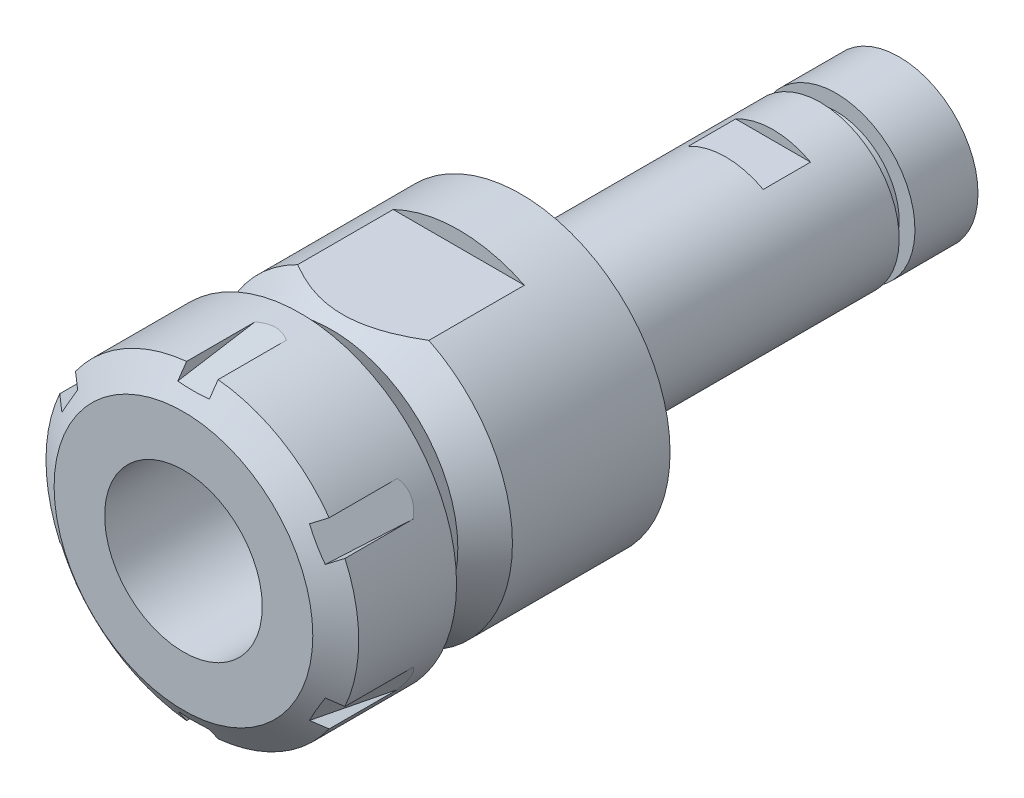
SolidWorks part; units mm, degrees
material "Chrome Stainless Steel"
ref_plane "Front Plane" through (0, 0, 0) normal (0, 0, 1) x (1, 0, 0)
ref_plane "Top Plane" through (0, 0, 0) normal (0, 1, 0) x (1, 0, 0)
ref_plane "Right Plane" through (0, 0, 0) normal (1, 0, 0) x (0, 0, -1)
sketch "Sketch1" plane through (0, 0, 0) normal (0, 0, 1) x (1, 0, 0)
  circle A0 centre (0, 0) radius 15.875
  dimension "D1" = 31.75
extrude "Boss-Extrude1" add sketch "Sketch1" along normal blind 101.6
sketch "Sketch2" plane through (0, 0, 101.6) normal (0, 0, 1) x (1, 0, 0)
  circle A0 centre (0, 0) radius 30.0482
  dimension "D1" = 60.0964
extrude "Boss-Extrude2" add sketch "Sketch2" along normal blind 31.75
sketch "Sketch5" plane through (0, 0, 0) normal (1, 0, 0) x (0, 0, -1)
  line L0 (-133.35, 30.0482) -> (-139.7, 25.4)
  line L1 (-139.7, 25.4) -> (-146.05, 30.0482)
  line L2 (-146.05, 30.0482) -> (-146.05, 0)
  line L3 (-146.05, 0) -> (-133.35, 0)
  line L4 (-133.35, 30.0482) -> (-133.35, -30.0482) construction
  line L5 (-133.35, 30.0482) -> (-133.35, 0)
  dimension "D1" = 12.7
  dimension "D2" = 6.35
  dimension "D3" = 4.6482
  dimension "D4" = 30.0482
revolve "Revolve1" add sketch "Sketch5" angle 360 about L3
sketch "Sketch6" plane through (0, 0, 146.05) normal (0, 0, 1) x (1, 0, 0)
  circle A0 centre (0, 0) radius 31.496
  dimension "D1" = 62.992
extrude "Boss-Extrude3" add sketch "Sketch6" along normal blind 23.5204
fillet "Fillet1" radius 2.54 1 edges at (15.875, 0, 0)
sketch "Sketch7" plane through (0, 0, 0) normal (0, 0, -1) x (-1, 0, 0)
  circle A0 centre (0, 0) radius 6.35
  dimension "D1" = 12.7
extrude "Cut-Extrude1" cut sketch "Sketch7" against normal blind 169.5704
sketch "Sketch8" plane through (0, 0, 169.5704) normal (0, 0, 1) x (1, 0, 0)
  circle A0 centre (0, 0) radius 15.875
  dimension "D1" = 31.75
extrude "Cut-Extrude2" cut sketch "Sketch8" against normal blind 36.2204
sketch "Sketch9" plane through (0, 0, 0) normal (1, 0, 0) x (0, 0, -1)
  line L0 (-114.1165, 30.0482) -> (-114.1165, -30.0482)
  line L1 (-101.6, 30.0482) -> (-133.35, 30.0482)
  line L2 (-101.6, 30.0482) -> (-101.6, -30.0482)
  line L3 (-101.6, -30.0482) -> (-133.35, -30.0482)
  line L4 (-133.35, 30.0482) -> (-133.35, -30.0482)
  line L5 (-133.35, 26.9875) -> (-114.1165, 26.9875)
  line L6 (-133.35, 0) -> (-114.1165, 0) construction
  line L7 (-133.35, 26.9875) -> (-137.5313, 26.9875)
  line L8 (-133.35, 30.0482) -> (-139.7, 25.4) construction
  line L9 (-137.5313, 26.9875) -> (-133.35, 30.0482)
  line L10 (-133.35, 30.0482) -> (-114.1165, 30.0482)
  line L11 (-133.35, -30.0482) -> (-114.1165, -30.0482)
  line L12 (-137.5313, -26.9875) -> (-133.35, -30.0482)
  line L13 (-133.35, -26.9875) -> (-137.5313, -26.9875)
  line L14 (-133.35, -26.9875) -> (-114.1165, -26.9875)
  dimension "D1" = 26.9875
extrude "Cut-Extrude3" cut sketch "Sketch9" against normal blind 48.26 and the other way blind 54.102 contours L4 L5 L0 L1 | L9 L7 L4 | L4 L13 L12 | L14 L4 L3 L0 region at (0, 28.5178, 123.7332) region at (0, 28.0077, 134.7438) region at (0, -28.5178, 123.7332) region at (0, -28.0077, 134.7438)
chamfer "Chamfer1" distance 3.81 angle 55 1 edges at (31.496, 0, 169.5704) first distance on face at (31.496, 0, 169.5704)
sketch "Sketch10" plane through (0, 0, 0) normal (1, 0, 0) x (0, 0, -1)
  line L0 (-151.0264, 31.496) -> (-167.6654, 28.7754)
  line L1 (-146.05, 31.496) -> (-165.7604, 31.496) construction
  line L2 (-165.7604, 31.496) -> (-169.5704, 26.0548) construction
  line L3 (-167.6654, 28.7754) -> (-167.6654, 34.7195)
  line L4 (-167.6654, 34.7195) -> (-151.0264, 31.496)
extrude "Cut-Extrude4" cut sketch "Sketch10" against normal blind 3.175 and the other way blind 3.175
pattern_circular "CirPattern1" count 6 over 360 about axis through (0, 0, 169.5704) along (0, 0, 1) of "Cut-Extrude4"
sketch "Sketch11" plane through (0, 26.9875, 0) normal (0, 1, 0) x (1, 0, 0)
  line L0 (15.875, -101.6) -> (15.875, -2.54) construction
  line L1 (15.875, -25.4) -> (-15.875, -25.4)
  line L2 (15.875, -25.4) -> (15.875, 0)
  line L3 (15.875, 0) -> (-15.875, 0)
  line L4 (-15.875, -25.4) -> (-15.875, 0)
  line L5 (13.335, 0) -> (-13.335, 0) construction
  dimension "D1" = 25.4
extrude "Cut-Extrude5" cut sketch "Sketch11" against normal blind 97.536
ref_axis "Axis1" through (0, 0, -8.4785) along (0, 0, 1)
ref_plane "Plane1" through (0, 0, 38.1) normal (0, 0, -1) x (-1, 0, 0)
sketch "Sketch12" plane through (0, 0, 38.1) normal (0, 0, -1) x (-1, 0, 0)
  circle A0 centre (0, 0) radius 19.1517
  circle A1 centre (0, 0) radius 12.7
  dimension "D1" = 25.4
extrude "Cut-Extrude6" cut sketch "Sketch12" against normal blind 3.175
ref_plane "Plane2" through (0, 0, 50.8) normal (0, 0, -1) x (-1, 0, 0)
sketch "Sketch13" plane through (0, 0, 50.8) normal (0, 0, -1) x (-1, 0, 0)
  line L0 (0, 6.35) -> (0, 13.97)
  line L1 (0, 13.97) -> (-7.5402, 13.97)
  line L2 (0, 13.97) -> (7.5402, 13.97)
  circle A0 centre (0, 0) radius 15.875
  circle A1 centre (0, 0) radius 6.35 construction
  dimension "D1" = 31.75
  dimension "D2" = 7.62
extrude "Cut-Extrude7" cut sketch "Sketch13" against normal blind 9.525 contours L2 A0 L1 region at (0, 14.7361, 50.8)
